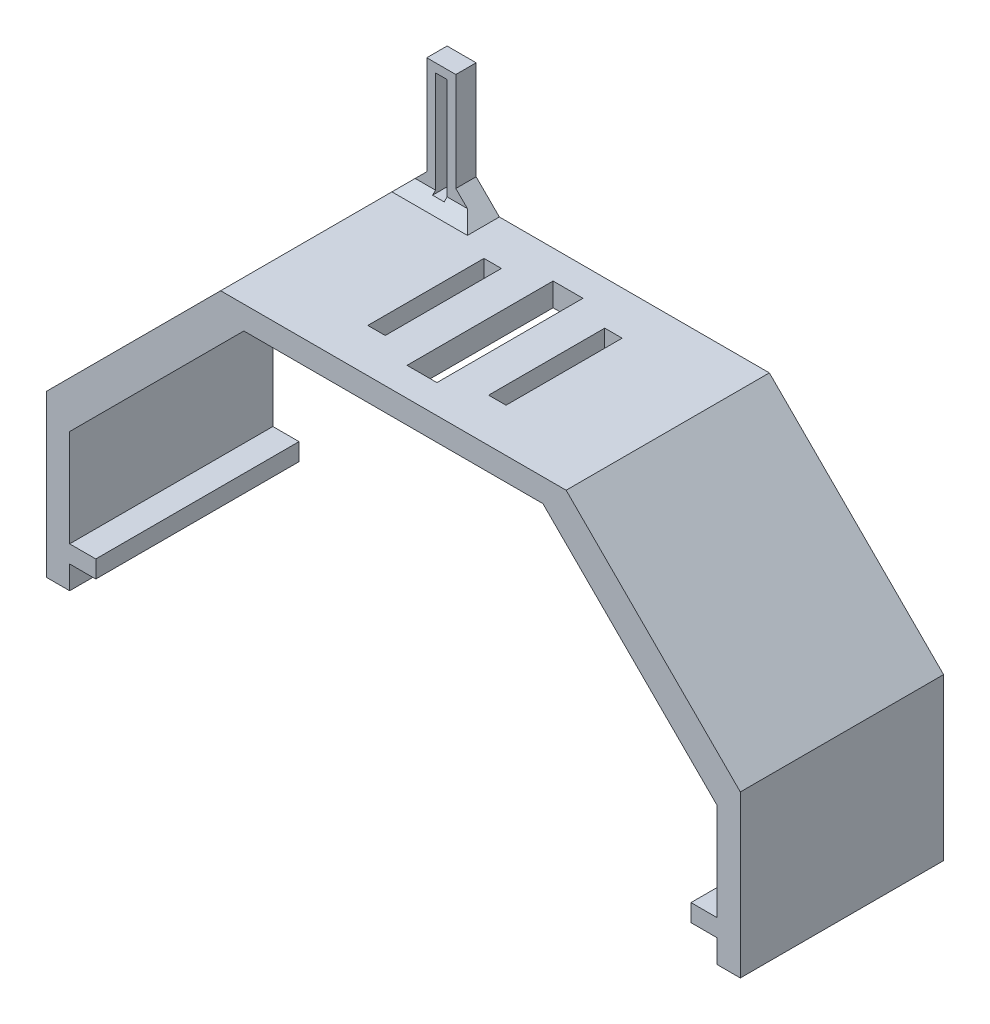
SolidWorks part; units mm, degrees
ref_plane "Front Plane" through (0, 0, 0) normal (0, 0, 1) x (1, 0, 0)
ref_plane "Top Plane" through (0, 0, 0) normal (0, 1, 0) x (1, 0, 0)
ref_plane "Right Plane" through (0, 0, 0) normal (1, 0, 0) x (0, 0, -1)
sketch "Sketch1" plane through (0, 0, 0) normal (0, 0, 1) x (1, 0, 0)
  line L0 (0, 0) -> (0, -32.6667) construction
  line L2 (55.75, -26.875) -> (55.75, -22.875)
  line L3 (55.75, 26.875) -> (-55.75, 26.875)
  line L4 (-55.75, -26.875) -> (-55.75, -22.875)
  line L7 (-55.75, 0) -> (55.75, 0) construction
  line L11 (-59.75, -26.875) -> (-59.75, 30.875)
  line L12 (59.75, 30.875) -> (-59.75, 30.875)
  line L13 (59.75, -26.875) -> (59.75, 30.875)
  line L15 (59.75, -30.875) -> (-59.75, -30.875) construction
  line L17 (55.75, -26.875) -> (-55.75, -26.875) construction
  line L36 (0, 0) -> (0, 26.875) construction
  line L46 (55.75, -26.875) -> (59.75, -26.875)
  line L47 (-55.75, -22.875) -> (-51.25, -22.875)
  line L48 (59.75, -30.875) -> (59.75, 30.875) construction
  line L49 (55.75, -26.875) -> (55.75, 26.875) construction
  line L52 (-55.75, -26.875) -> (-59.75, -26.875)
  line L53 (-59.75, -30.875) -> (-59.75, 30.875) construction
  line L54 (-59.5611, -22.875) -> (-10.25, -22.875) construction
  line L55 (-51.25, -22.875) -> (-51.25, -19.875)
  line L56 (-51.25, -19.875) -> (-55.75, -19.875)
  line L57 (-55.75, -19.875) -> (-55.75, 26.875)
  line L58 (-55.75, -26.875) -> (-55.75, 26.875) construction
  line L59 (55.75, -22.875) -> (51.25, -22.875)
  line L60 (51.25, -22.875) -> (51.25, -19.875)
  line L61 (51.25, -19.875) -> (55.75, -19.875)
  line L62 (55.75, -19.875) -> (55.75, 26.875)
  point P0 (0, 0)
  dimension "D1" = 55.75
  dimension "D2" = 4.5
  dimension "D3" = 3
  dimension "D9" = 53.75
  dimension "D4" = 4
extrude "Boss-Extrude1" add sketch "Sketch1" against normal mid plane 35
chamfer "Chamfer1" distance 30 angle 45 4 edges at (59.75, 30.875, 0) (-59.75, 30.875, 0) (55.75, 26.875, 0) (-55.75, 26.875, 0)
sketch "Sketch6" plane through (0, 30.875, 0) normal (0, 1, 0) x (1, 0, 0)
  line L1 (-2.575, 12.575) -> (2.575, 12.575)
  line L2 (-2.575, 12.575) -> (-2.575, -12.575)
  line L3 (-2.575, -12.575) -> (2.575, -12.575)
  line L4 (2.575, 12.575) -> (2.575, -12.575)
  line L5 (-2.575, 12.575) -> (2.575, -12.575) construction
  line L6 (-2.575, -12.575) -> (2.575, 12.575) construction
  point P0 (0, 0)
  dimension "D1" = 5.15
  dimension "D2" = 25.15
extrude "Cut-Extrude2" cut sketch "Sketch6" against normal blind 4
sketch "Sketch7" plane through (0, 30.875, 0) normal (0, 1, 0) x (1, 0, 0)
  line L0 (-10.4, 0) -> (10.4, 0) construction
  line L2 (11.9, 10) -> (8.9, 10)
  line L3 (11.9, 10) -> (11.9, -10)
  line L4 (11.9, -10) -> (8.9, -10)
  line L5 (8.9, 10) -> (8.9, -10)
  line L6 (11.9, 10) -> (8.9, -10) construction
  line L7 (11.9, -10) -> (8.9, 10) construction
  line L8 (-8.9, 10) -> (-11.9, 10)
  line L9 (-8.9, 10) -> (-8.9, -10)
  line L10 (-8.9, -10) -> (-11.9, -10)
  line L11 (-11.9, 10) -> (-11.9, -10)
  line L12 (-8.9, 10) -> (-11.9, -10) construction
  line L13 (-8.9, -10) -> (-11.9, 10) construction
  point P4 (0, 0)
  dimension "D1" = 20
  dimension "D2" = 3
  dimension "D3" = 3
  dimension "D4" = 20
extrude "Cut-Extrude3" cut sketch "Sketch7" against normal blind 10
sketch "Sketch8" plane through (0, 0, -17.5) normal (0, 0, 1) x (1, 0, 0)
  line L0 (-22.25, 32.375) -> (-22.25, 50.375)
  line L1 (-25.75, 26.875) -> (-20.75, 26.875)
  line L2 (-25.75, 26.875) -> (-25.75, 51.875)
  line L3 (-25.75, 51.875) -> (-20.75, 51.875)
  line L4 (-20.75, 26.875) -> (-20.75, 51.875)
  line L5 (-24.25, 32.375) -> (-24.25, 50.375)
  line L6 (-24.25, 50.375) -> (-22.25, 50.375)
  line L8 (-22.25, 26.875) -> (-22.25, 51.875) construction
  line L9 (29.75, 32.375) -> (-29.75, 32.375)
  line L10 (-22.25, 32.375) -> (-24.25, 32.375)
  line L11 (-24.25, 26.875) -> (-24.25, 51.875) construction
  line L12 (-25.75, 50.375) -> (-20.75, 50.375) construction
  dimension "D1" = 25
  dimension "D2" = 5
  dimension "D3" = 1.5
  dimension "D4" = 1.5
  dimension "D5" = 1.5
  dimension "D6" = 1.5
extrude "Boss-Extrude2" add sketch "Sketch8" along normal blind 3.5
chamfer "Chamfer2" distance 4 angle 45 2 edges at (-25.75, 30.875, -15.75) (-20.75, 30.875, -15.75)
chamfer "Chamfer3" distance 2 angle 45 1 edges at (-23.25, 30.875, -14)
